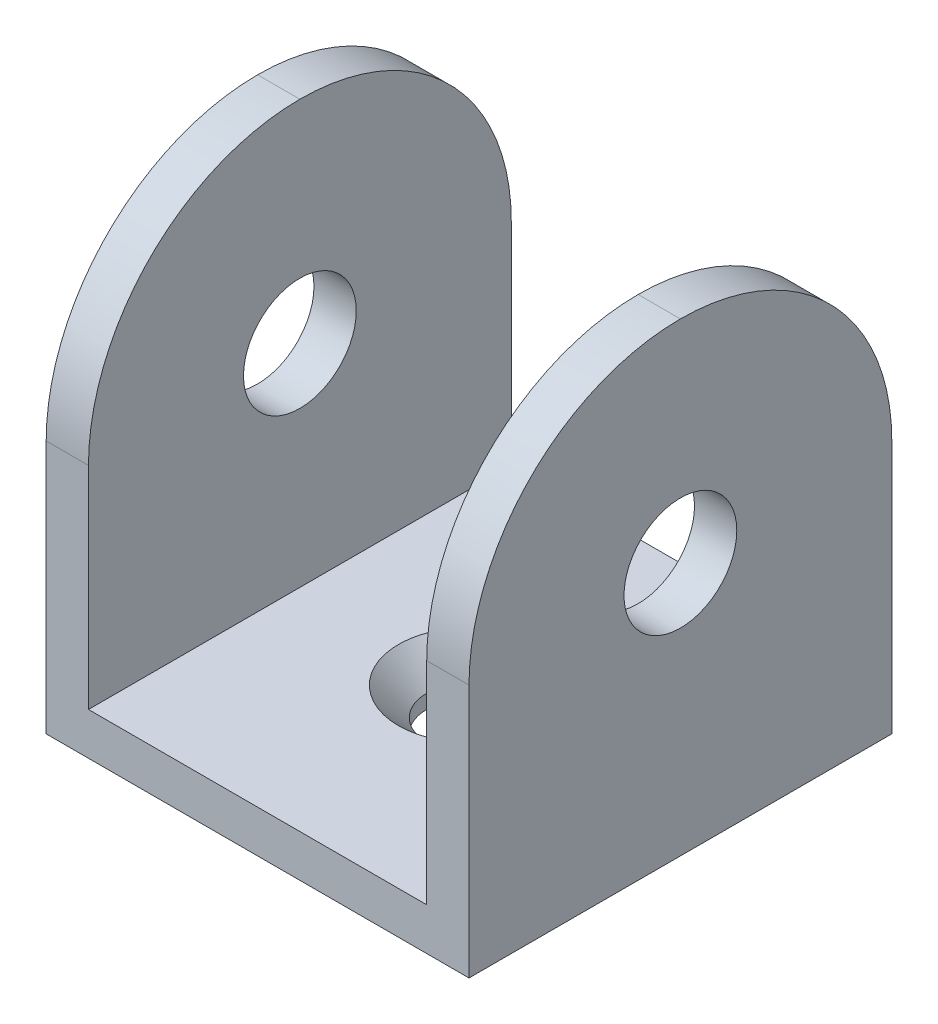
SolidWorks part; units mm, degrees
ref_plane "Alzado" through (0, 0, 0) normal (0, 0, 1) x (1, 0, 0)
ref_plane "Planta" through (0, 0, 0) normal (0, 1, 0) x (1, 0, 0)
ref_plane "Vista lateral" through (0, 0, 0) normal (1, 0, 0) x (0, 0, -1)
sketch "Croquis1" plane through (0, 0, 0) normal (0, 1, 0) x (1, 0, 0)
  line L1 (15, -15) -> (-15, -15)
  line L2 (15, -15) -> (15, 15)
  line L3 (15, 15) -> (-15, 15)
  line L4 (-15, -15) -> (-15, 15)
  line L5 (15, -15) -> (-15, 15) construction
  line L6 (15, 15) -> (-15, -15) construction
  point P0 (0, 0)
  dimension "D1" = 30
extrude "Saliente-Extruir1" add sketch "Croquis1" along normal blind 3
sketch "Croquis2" plane through (0, 3, 0) normal (0, 1, 0) x (1, 0, 0)
  line L0 (-15, -15) -> (15, -15) construction
  line L1 (-15, 15) -> (-12, 15)
  line L2 (-15, 15) -> (-15, -15)
  line L3 (-15, -15) -> (-12, -15)
  line L4 (-12, 15) -> (-12, -15)
  line L6 (15, 15) -> (12, 15)
  line L7 (15, 15) -> (15, -15)
  line L8 (15, -15) -> (12, -15)
  line L9 (12, 15) -> (12, -15)
  dimension "D1" = 3
extrude "Saliente-Extruir2" add sketch "Croquis2" along normal blind 30
fillet "Redondeo1" radius 15 4 edges at (-13.5, 33, -15) (13.5, 33, -15) (13.5, 33, 15) (-13.5, 33, 15)
sketch "Croquis3" plane through (15, 0, 0) normal (1, 0, 0) x (0, 0, -1)
  circle A0 centre (0, 18) radius 4
  dimension "D1" = 8
extrude "Cortar-Extruir1" cut sketch "Croquis3" against normal through all
sketch "Croquis4" plane through (0, 3, 0) normal (0, 1, 0) x (1, 0, 0)
  circle A0 centre (0, 0) radius 3
  dimension "D1" = 6
extrude "Cortar-Extruir2" cut sketch "Croquis4" against normal through all
chamfer "Chaflán1" distance 2 angle 45 1 edges at (0, 3, 3)
